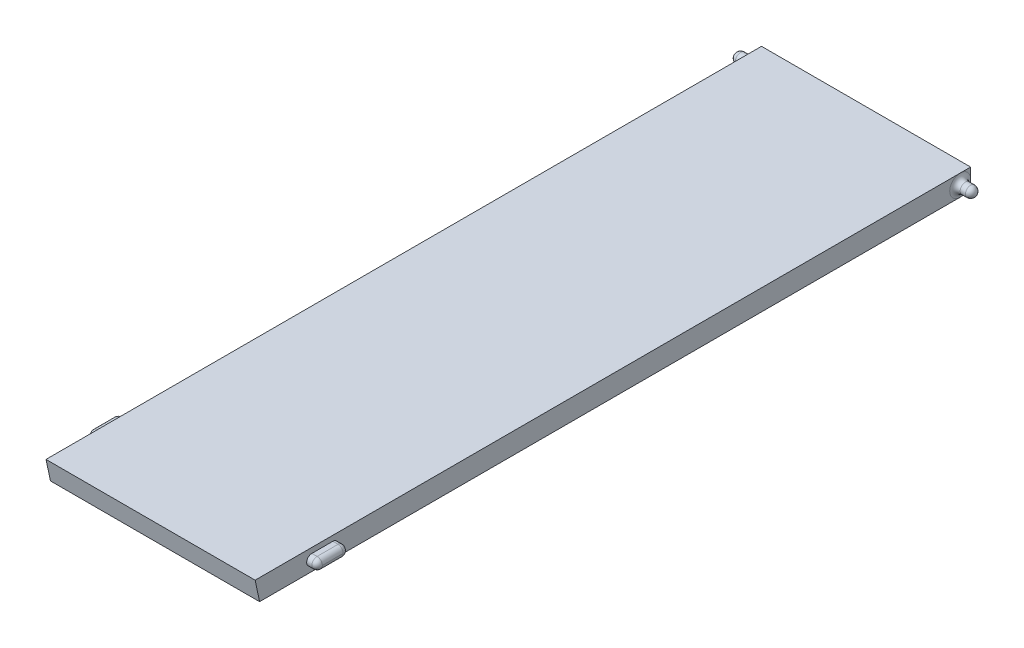
SolidWorks part; units mm, degrees
ref_plane "Front Plane" through (0, 0, 0) normal (0, 0, 1) x (1, 0, 0)
ref_plane "Top Plane" through (0, 0, 0) normal (0, 1, 0) x (1, 0, 0)
ref_plane "Right Plane" through (0, 0, 0) normal (1, 0, 0) x (0, 0, -1)
sketch "Sketch1" plane through (0, 0, 0) normal (0, 1, 0) x (1, 0, 0)
  line L1 (-10, 34) -> (10, 34)
  line L2 (-10, 34) -> (-10, -34)
  line L3 (-10, -34) -> (10, -34)
  line L4 (10, 34) -> (10, -34)
  line L5 (-10, 34) -> (10, -34) construction
  line L6 (-10, -34) -> (10, 34) construction
  point P0 (0, 0)
  dimension "D1" = 20
  dimension "D2" = 68
extrude "Boss-Extrude1" add sketch "Sketch1" along normal blind 2
ref_plane "Plane1" through (0, 0, 0) normal (1, 0, 0) x (0, 0, -1)
sketch "Sketch2" plane through (0, 0, 0) normal (1, 0, 0) x (0, 0, -1)
  line L0 (-34, 1) -> (34, 1) construction
  line L1 (-34, 2) -> (-34, 0) construction
  line L2 (34, 2) -> (34, 0) construction
  circle A0 centre (33, 1) radius 0.5
  point P2 (34.2338, 1.2621)
  point P9 (34.2581, 1)
  point P10 (33.7903, 1.217)
  dimension "D2" = 1
  dimension "D1" = 1
extrude "Boss-Extrude2" add sketch "Sketch2" along normal blind 1.5 from surface at 10 starting at face at (10, 1, 0)
fillet "Fillet1" radius 0.5 1 edges at (11.5, 1, -32.5)
fillet "Fillet4" radius 0.5 1 edges at (10, 1, -32.5)
mirror "Mirror2" about plane through (0, 0, 0) normal (1, 0, 0) of "Fillet4", "Boss-Extrude2", "Fillet1"
fillet "Fillet2" radius 1 1 edges at (0, 0, -34)
sketch "Sketch3" plane through (0, 0, 0) normal (1, 0, 0) x (0, 0, -1)
  line L0 (-34, 2) -> (-34.428, 2)
  line L1 (-34.428, 2) -> (-34, 0)
  line L2 (-34, 0) -> (-34, 2)
  dimension "D1" = 12.08
extrude "Boss-Extrude3" add sketch "Sketch3" along normal up to surface and the other way up to surface up to face at (10, 1, 0.75) other way up to face at (-10, 1, 0.75)
sketch "Sketch4" plane through (0, 0, 0) normal (1, 0, 0) x (0, 0, -1)
  line L0 (-27, 1) -> (-29, 1) construction
  line L1 (-27, 0.5) -> (-29, 0.5)
  line L2 (-27, 1.5) -> (-29, 1.5)
  arc A0 (-27, 0.5) -> (-27, 1.5) centre (-27, 1) ccw
  arc A1 (-29, 1.5) -> (-29, 0.5) centre (-29, 1) ccw
  point P2 (-28, 1)
  point P7 (0, 0)
  point P9 (33, 1)
  dimension "D1" = 1
  dimension "D2" = 2
  dimension "D3" = 61
extrude "Boss-Extrude4" add sketch "Sketch4" along normal blind 1 from surface at 10 starting at face at (10, 1, 0.857)
fillet "Fillet3" radius 0.5 4 edges at (11, 1, 26.5) (11, 0.5, 28) (11, 1, 29.5) (11, 1.5, 28)
mirror "Mirror4" about plane through (0, 0, 0) normal (1, 0, 0) of "Fillet3", "Boss-Extrude4"
